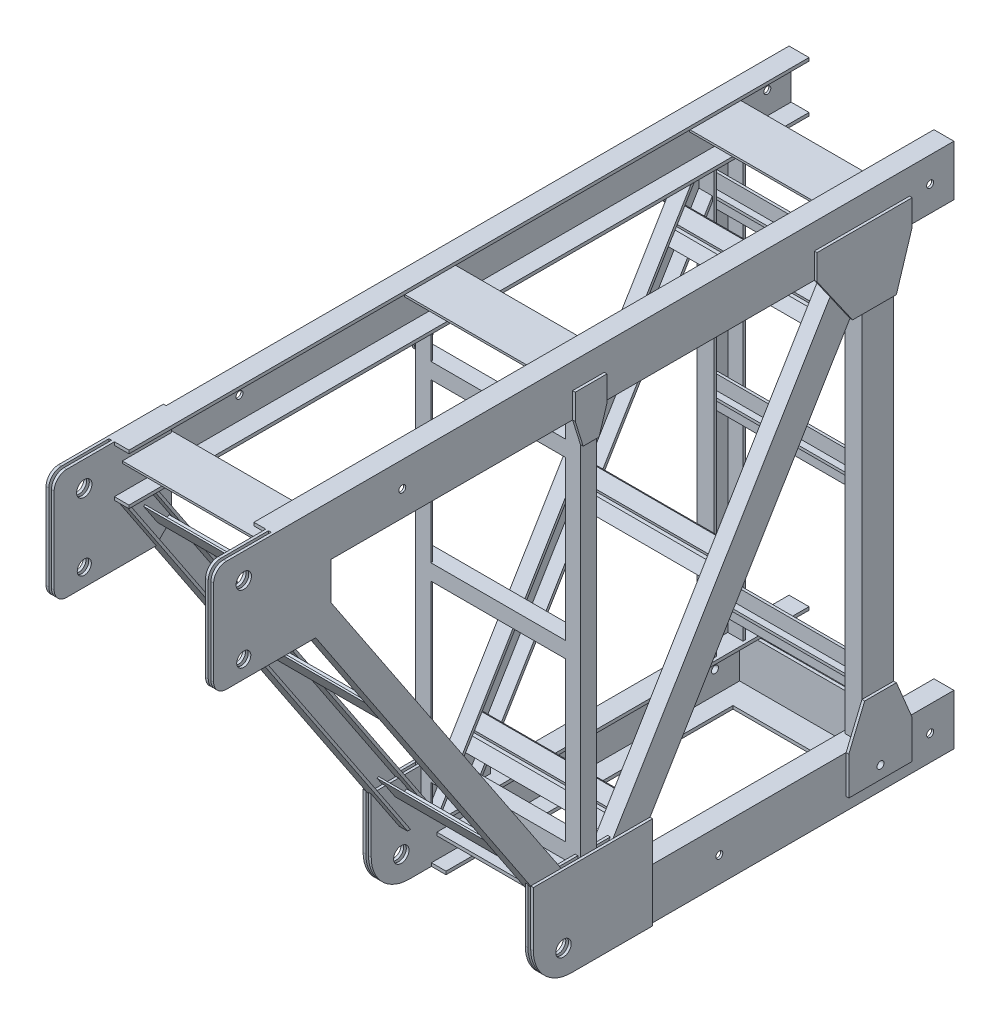
SolidWorks part; units mm, degrees
note: The reader was unsure of these and kept them because the rebuilt part matched: shared geometry of "草图38<2>".
ref_plane "前视基准面" through (0, 0, 0) normal (0, 0, 1) x (1, 0, 0)
ref_plane "上视基准面" through (0, 0, 0) normal (0, 1, 0) x (1, 0, 0)
ref_plane "右视基准面" through (0, 0, 0) normal (1, 0, 0) x (0, 0, -1)
sketch "草图2" plane through (0, 0, 0) normal (0, 0, 1) x (1, 0, 0)
  line L0 (0, 0) -> (0, 160)
  line L1 (0, 160) -> (63, 160)
  line L2 (63, 160) -> (63, 150)
  line L3 (63, 150) -> (6.5, 150)
  line L4 (6.5, 150) -> (6.5, 10)
  line L5 (6.5, 10) -> (63, 10)
  line L6 (63, 10) -> (63, 0)
  line L7 (63, 0) -> (0, 0)
  line L8 (457, 160) -> (520, 160)
  line L9 (520, 160) -> (520, 0)
  line L10 (520, 0) -> (457, 0)
  line L11 (457, 0) -> (457, 10)
  line L12 (457, 10) -> (513.5, 10)
  line L13 (513.5, 10) -> (513.5, 150)
  line L14 (513.5, 150) -> (457, 150)
  line L15 (457, 150) -> (457, 160)
  dimension "D1" = 160
  dimension "D2" = 10
  dimension "D3" = 6.5
  dimension "D4" = 63
  dimension "D5" = 520
extrude "拉伸1" add sketch "草图2" along normal blind 2335
pattern_linear "阵列(线性)2" count 2 spacing 1500 along (0, -1, 0) of "拉伸1"
sketch "草图4" plane through (0, -1340, 0) normal (0, 1, 0) x (1, 0, 0)
  line L0 (0, -2335) -> (0, 0) construction
  line L1 (520, -2335) -> (0, -2335)
  line L2 (520, -2335) -> (520, -1335)
  line L3 (520, -1335) -> (0, -1335)
  line L4 (0, -2335) -> (0, -1335)
  dimension "D1" = 1000
extrude "拉伸2" cut sketch "草图4" against normal blind 1000
sketch "草图5" plane through (0, 0, 0) normal (-1, 0, 0) x (0, 0, 1)
  line L0 (160, 95) -> (320, 95)
  line L1 (320, 95) -> (320, 88.5)
  line L2 (243.25, 88.5) -> (320, 88.5)
  line L3 (243.25, 88.5) -> (243.25, 48.5)
  line L4 (243.25, 48.5) -> (236.75, 48.5)
  line L5 (236.75, 48.5) -> (236.75, 88.5)
  line L6 (236.75, 88.5) -> (160, 88.5)
  line L7 (160, 88.5) -> (160, 95)
  line L8 (0, 160) -> (0, 0) construction
  point P10 (0, 80)
  dimension "D1" = 160
  dimension "D2" = 6.5
  dimension "D3" = 6.5
  dimension "D4" = 40
  dimension "D5" = 160
  dimension "D6" = 15
extrude "拉伸3" add sketch "草图5" against normal blind 520
sketch "草图8" plane through (0, 0, 0) normal (-1, 0, 0) x (0, 0, 1)
  line L0 (240, -1420) -> (240, 160) construction
  line L1 (2335, 160) -> (0, 160) construction
  line L2 (2335, 0) -> (0, 0) construction
  line L3 (190, 0) -> (290, 0)
  line L4 (190, 0) -> (190, -1340)
  line L5 (190, -1340) -> (290, -1340)
  line L6 (290, 0) -> (290, -1340)
  line L7 (1335, -1340) -> (0, -1340) construction
  line L8 (1335, -1500) -> (0, -1500) construction
  line L9 (0, -1340) -> (0, -1500) construction
  dimension "D1" = 50
  dimension "D2" = 50
  dimension "D3" = 80
  dimension "D4" = 240
extrude "拉伸7" add sketch "草图8" against normal blind 520 separate body
sketch "草图10" plane through (0, -1340, 0) normal (0, -1, 0) x (1, 0, 0)
  line L0 (466.7, 290) -> (466.7, 281.5)
  line L1 (520, 290) -> (0, 290) construction
  line L2 (466.7, 281.5) -> (514.7, 281.5)
  line L3 (514.7, 281.5) -> (514.7, 198.5)
  line L4 (514.7, 198.5) -> (466.7, 198.5)
  line L5 (466.7, 198.5) -> (466.7, 190)
  line L6 (520, 190) -> (0, 190) construction
  line L7 (53.3, 190) -> (53.3, 198.5)
  line L8 (53.3, 198.5) -> (5.3, 198.5)
  line L9 (5.3, 198.5) -> (5.3, 281.5)
  line L10 (53.3, 281.5) -> (53.3, 290)
  line L11 (53.3, 290) -> (466.7, 290)
  line L12 (5.3, 281.5) -> (53.3, 281.5)
  line L13 (53.3, 190) -> (466.7, 190)
  line L16 (0, 1335) -> (0, 0) construction
  line L17 (520, 1335) -> (520, 0) construction
  dimension "D1" = 5.3
  dimension "D2" = 5.3
  dimension "D3" = 8.5
  dimension "D4" = 48
extrude "拉伸9" cut sketch "草图10" against normal blind 1340
sketch "草图11" plane through (0, 0, 0) normal (-1, 0, 0) x (0, 0, 1)
  line L0 (2335, 160) -> (2335, 0) construction
  line L1 (2335, 80) -> (0, 80) construction
  line L2 (0, 160) -> (0, 0) construction
  circle A0 centre (2240, 80) radius 11
  dimension "D1" = 22
  dimension "D2" = 95
extrude "拉伸10" cut sketch "草图11" against normal through all
sketch "草图12" plane through (0, 0, 0) normal (-1, 0, 0) x (0, 0, 1)
  line L0 (1145, -1420) -> (290, 0) construction
  line L1 (290, 0) -> (348.3639, 0)
  line L2 (2335, 0) -> (0, 0) construction
  line L3 (348.3639, 0) -> (1155.1949, -1340)
  line L4 (1155.1949, -1340) -> (1038.467, -1340)
  line L5 (1038.467, -1340) -> (290, -96.9319)
  line L6 (290, -1340) -> (290, 0) construction
  line L7 (290, -96.9319) -> (290, 0)
  line L8 (0, -1420) -> (1335, -1420) construction
  line L9 (1335, -1340) -> (0, -1340) construction
  line L10 (0, -1340) -> (0, -1500) construction
  line L11 (1335, -1500) -> (1335, -1340) construction
  dimension "D1" = 50
  dimension "D2" = 50
  dimension "D3" = 190
extrude "拉伸11" add sketch "草图12" against normal blind 48
pattern_linear "阵列(线性)3" count 2 spacing 472 along (1, 0, 0) of "拉伸11"
sketch "草图13" plane through (48, 0, 0) normal (1, 0, 0) x (0, 0, -1)
  line L0 (-338.4421, 0) -> (-290, 0)
  line L1 (-348.3639, 0) -> (-290, 0) construction
  line L2 (-290, 0) -> (-290, -80.4535)
  line L3 (-290, 0) -> (-290, -96.9319) construction
  line L4 (-290, -80.4535) -> (-1048.3889, -1340)
  line L5 (-1038.467, -1340) -> (-1155.1949, -1340) construction
  line L6 (-1048.3889, -1340) -> (-1145.2731, -1340)
  line L7 (-1145.2731, -1340) -> (-338.4421, 0)
  line L8 (-1155.1949, -1340) -> (-348.3639, 0) construction
  line L9 (-290, -96.9319) -> (-1038.467, -1340) construction
  dimension "D1" = 8.5
  dimension "D2" = 8.5
extrude "拉伸12" cut sketch "草图13" against normal blind 42.7
sketch "草图14" plane through (472, 0, 0) normal (-1, 0, 0) x (0, 0, 1)
  line L0 (290, -80.4535) -> (290, 0)
  line L1 (290, 0) -> (290, -96.9319) construction
  line L2 (290, 0) -> (338.4421, 0)
  line L3 (348.3639, 0) -> (290, 0) construction
  line L4 (338.4421, 0) -> (1145.2731, -1340)
  line L5 (1038.467, -1340) -> (1155.1949, -1340) construction
  line L6 (1145.2731, -1340) -> (1048.3889, -1340)
  line L7 (1048.3889, -1340) -> (290, -80.4535)
  line L8 (1155.1949, -1340) -> (348.3639, 0) construction
  line L9 (290, -96.9319) -> (1038.467, -1340) construction
  dimension "D1" = 8.5
  dimension "D2" = 8.5
extrude "拉伸13" cut sketch "草图14" against normal blind 42.7
sketch "草图15" plane through (0, 0, 0) normal (-1, 0, 0) x (0, 0, 1)
  line L0 (2145, 80) -> (1145, -1420) construction
  line L1 (2091.6667, 0) -> (2043.5926, 0)
  line L2 (2335, 0) -> (348.3639, 0) construction
  line L3 (2043.5926, 0) -> (1152.8527, -1336.11)
  line L4 (1155.1949, -1340) -> (348.3639, 0) construction
  line L5 (1152.8527, -1336.11) -> (1155.1949, -1340)
  line L6 (1155.1949, -1340) -> (1246.4074, -1340)
  line L7 (1335, -1340) -> (1155.1949, -1340) construction
  line L8 (1246.4074, -1340) -> (2139.7407, 0)
  line L9 (2139.7407, 0) -> (2091.6667, 0)
  line L10 (0, -1420) -> (1335, -1420) construction
  line L11 (2240, 80) -> (0, 80) construction
  line L12 (0, 160) -> (0, 0) construction
  line L13 (0, -1340) -> (0, -1500) construction
  line L14 (1335, -1500) -> (1335, -1340) construction
  dimension "D1" = 40
  dimension "D2" = 40
  dimension "D3" = 190
  dimension "D4" = 95
extrude "拉伸14" add sketch "草图15" against normal blind 43
pattern_linear "阵列(线性)4" count 2 spacing 477 along (1, 0, 0) of "拉伸14"
sketch "草图16" plane through (477, 0, 0) normal (-1, 0, 0) x (0, 0, 1)
  line L0 (2053.2075, 0) -> (2130.1259, 0)
  line L1 (2139.7407, 0) -> (2043.5926, 0) construction
  line L2 (2130.1259, 0) -> (1236.7925, -1340)
  line L3 (1155.1949, -1340) -> (1246.4074, -1340) construction
  line L4 (1236.7925, -1340) -> (1159.8741, -1340)
  line L5 (1159.8741, -1340) -> (2053.2075, 0)
  line L6 (1246.4074, -1340) -> (2139.7407, 0) construction
  line L7 (2043.5926, 0) -> (1152.8527, -1336.11) construction
  dimension "D1" = 8
  dimension "D2" = 8
extrude "拉伸15" cut sketch "草图16" against normal blind 38
sketch "草图17" plane through (43, 0, 0) normal (1, 0, 0) x (0, 0, -1)
  line L0 (-2130.1259, 0) -> (-2053.2075, 0)
  line L1 (-2139.7407, 0) -> (-2043.5926, 0) construction
  line L2 (-2053.2075, 0) -> (-1159.8741, -1340)
  line L3 (-1155.1949, -1340) -> (-1246.4074, -1340) construction
  line L4 (-1159.8741, -1340) -> (-1236.7925, -1340)
  line L5 (-1236.7925, -1340) -> (-2130.1259, 0)
  line L6 (-1246.4074, -1340) -> (-2139.7407, 0) construction
  line L7 (-2043.5926, 0) -> (-1152.8527, -1336.11) construction
  dimension "D1" = 8
  dimension "D2" = 8
extrude "拉伸16" cut sketch "草图17" against normal blind 38
sketch "草图18" plane through (0, 0, 0) normal (-1, 0, 0) x (0, 0, 1)
  line L0 (1152.8527, -1336.11) -> (1152.8527, 0.0067) construction
  line L1 (1152.8527, -1336.11) -> (348.3639, 0) construction
  line L2 (2043.5926, 0) -> (348.3639, 0) construction
  line L4 (1127.8527, 0) -> (1177.8527, 0)
  line L5 (1127.8527, 0) -> (1127.8527, -1294.5895)
  line L7 (1177.8527, 0) -> (1177.8527, -1298.61)
  line L8 (2043.5926, 0) -> (1152.8527, -1336.11) construction
  line L9 (1177.8527, -1298.61) -> (1152.8527, -1336.11)
  line L10 (1152.8527, -1336.11) -> (1127.8527, -1294.5895)
  dimension "D1" = 25
  dimension "D2" = 25
extrude "拉伸17" add sketch "草图18" against normal blind 520 separate body
sketch "草图19" plane through (0, 0, 0) normal (0, 1, 0) x (1, 0, 0)
  line L0 (457, -2335) -> (457, 0) construction
  line L1 (457, -1127.8527) -> (63, -1127.8527)
  line L2 (457, -1127.8527) -> (457, -1177.8527)
  line L3 (457, -1177.8527) -> (63, -1177.8527)
  line L4 (63, -1127.8527) -> (63, -1177.8527)
  line L5 (520, -1127.8527) -> (0, -1127.8527) construction
  line L6 (520, -1177.8527) -> (0, -1177.8527) construction
  line L7 (63, -2335) -> (63, 0) construction
extrude "拉伸18" cut sketch "草图19" against normal through all
sketch "草图20" plane through (457, 0, 0) normal (-1, 0, 0) x (0, 0, 1)
  line L0 (1127.8527, 0) -> (1177.8527, 0)
  line L1 (1177.8527, 0) -> (1177.8527, -1298.61)
  line L2 (1177.8527, -1298.61) -> (1152.8527, -1336.11)
  line L3 (1152.8527, -1336.11) -> (1127.8527, -1294.5895)
  line L4 (1127.8527, -1294.5895) -> (1152.8527, -1336.11) construction
  line L5 (1127.8527, -1294.5895) -> (1127.8527, 0) construction
  line L6 (1127.8527, -1294.5895) -> (1127.8527, 0)
extrude "拉伸19" cut sketch "草图20" against normal blind 15
sketch "草图21" plane through (63, 0, 0) normal (1, 0, 0) x (0, 0, -1)
  line L0 (-1177.8527, -1298.61) -> (-1152.8527, -1336.11)
  line L1 (-1152.8527, -1336.11) -> (-1127.8527, -1294.5895)
  line L2 (-1127.8527, -1294.5895) -> (-1127.8527, 0)
  line L3 (-2335, 0) -> (0, 0) construction
  line L4 (-1127.8527, -1294.5895) -> (-1127.8527, 0) construction
  line L5 (-1127.8527, 0) -> (-1177.8527, 0)
  line L6 (-1127.8527, 0) -> (-1177.8527, 0) construction
  line L7 (-1177.8527, 0) -> (-1177.8527, -1298.61)
extrude "拉伸20" cut sketch "草图21" against normal blind 15
sketch "草图23" plane through (472, 0, 0) normal (-1, 0, 0) x (0, 0, 1)
  line L0 (1172.8527, -1306.11) -> (1152.8527, -1336.11)
  line L1 (1152.8527, -1336.11) -> (1177.8527, -1298.61) construction
  line L2 (1152.8527, -1336.11) -> (1127.8527, -1294.5895)
  line L3 (1127.8527, -1294.5895) -> (1127.8527, 0)
  line L4 (1177.8527, 0) -> (1127.8527, 0) construction
  line L5 (1127.8527, 0) -> (1172.8527, 0)
  line L6 (1172.8527, 0) -> (1172.8527, -1306.11)
  line L8 (1177.8527, -1298.61) -> (1177.8527, 0) construction
  dimension "D1" = 5
extrude "拉伸21" cut sketch "草图23" against normal blind 45
sketch "草图24" plane through (48, 0, 0) normal (1, 0, 0) x (0, 0, -1)
  line L0 (-1172.8527, -1306.11) -> (-1152.8527, -1336.11)
  line L1 (-1177.8527, -1298.61) -> (-1152.8527, -1336.11) construction
  line L2 (-1152.8527, -1336.11) -> (-1127.8527, -1294.5895)
  line L3 (-1127.8527, -1294.5895) -> (-1127.8527, 0)
  line L4 (-1127.8527, 0) -> (-1172.8527, 0)
  line L5 (-1127.8527, 0) -> (-1177.8527, 0) construction
  line L6 (-1172.8527, 0) -> (-1172.8527, -1306.11)
  line L7 (-1177.8527, 0) -> (-1177.8527, -1298.61) construction
  dimension "D1" = 5
extrude "拉伸22" cut sketch "草图24" against normal blind 45
pattern_linear "阵列(线性)6" count 3 spacing 900 along (0, 0, 1) of "拉伸3"
sketch "草图27" plane through (0, -1500, 0) normal (0, -1, 0) x (1, 0, 0)
  line L0 (0, 1335) -> (0, 0) construction
  line L1 (0, 240) -> (520, 240)
  line L2 (0, 240) -> (0, 80)
  line L3 (0, 80) -> (520, 80)
  line L4 (520, 240) -> (520, 80)
  line L5 (520, 1335) -> (520, 0) construction
  line L6 (0, 0) -> (63, 0) construction
  line L12 (0, 160) -> (520, 160) construction
  dimension "D1" = 160
  dimension "D2" = 80
extrude "拉伸24" add sketch "草图27" against normal blind 10
sketch "草图28" plane through (0, -1490, 0) normal (0, 1, 0) x (1, 0, 0)
  line L0 (513.5, -1335) -> (513.5, 0) construction
  line L1 (513.5, -162.5) -> (6.5, -162.5)
  line L2 (513.5, -162.5) -> (513.5, -152.5)
  line L3 (513.5, -152.5) -> (6.5, -152.5)
  line L4 (6.5, -162.5) -> (6.5, -152.5)
  line L5 (6.5, -1335) -> (6.5, 0) construction
  line L6 (63, -240) -> (63, -80) construction
  line L7 (457, -240) -> (457, -80) construction
  line L8 (63, -80) -> (457, -80) construction
  line L9 (457, -160) -> (63, -160) construction
  dimension "D1" = 10
  dimension "D2" = 5
extrude "拉伸25" add sketch "草图28" along normal blind 140
sketch "草图29" plane through (0, 0, 0) normal (-1, 0, 0) x (0, 0, 1)
  line L0 (240, -1340) -> (190, -1340) construction
  line L1 (240, -1340) -> (240, 160) construction
  line L2 (2335, 160) -> (0, 160) construction
  line L3 (231.5, -1160) -> (231.5, -1260)
  line L4 (231.5, -1260) -> (240, -1260)
  line L5 (240, -1260) -> (240, -1214.25)
  line L6 (240, -1214.25) -> (260, -1214.25)
  line L7 (260, -1214.25) -> (260, -1205.75)
  line L8 (260, -1205.75) -> (240, -1205.75)
  line L9 (240, -1205.75) -> (240, -1160)
  line L10 (240, -1160) -> (231.5, -1160)
  line L11 (190, 0) -> (190, -1340) construction
  line L12 (240, -1340) -> (290, -1340) construction
  dimension "D1" = 100
  dimension "D2" = 8.5
  dimension "D3" = 8.5
  dimension "D4" = 20
  dimension "D5" = 80
extrude "拉伸26" add sketch "草图29" against normal blind 520
pattern_linear "阵列(线性)9" count 3 spacing 550 along (0, 1, 0) of "拉伸26"
sketch "草图30" plane through (0, 0, 0) normal (-1, 0, 0) x (0, 0, 1)
  line L0 (1193.169, -1500) -> (193.662, 160) construction
  line L1 (1335, -1500) -> (0, -1500) construction
  line L2 (2335, 160) -> (0, 160) construction
  line L3 (290, -96.9319) -> (1038.467, -1340) construction
  line L5 (290, -96.9319) -> (332.8347, -71.1406) construction
  line L6 (332.8347, -71.1406) -> (375.6693, -45.3493) construction
  line L7 (1152.8527, -1336.11) -> (348.3639, 0) construction
  line L8 (339.5134, -98.7113) -> (391.096, -184.3806)
  line L9 (391.096, -184.3806) -> (398.3779, -179.9961)
  line L10 (398.3779, -179.9961) -> (374.7789, -140.8024)
  line L11 (374.7789, -140.8024) -> (391.9128, -130.4859)
  line L12 (391.9128, -130.4859) -> (387.5282, -123.204)
  line L13 (387.5282, -123.204) -> (370.3944, -133.5205)
  line L14 (370.3944, -133.5205) -> (346.7953, -94.3268)
  line L15 (346.7953, -94.3268) -> (339.5134, -98.7113)
  dimension "D1" = 100
  dimension "D2" = 8.5
  dimension "D3" = 8.5
  dimension "D4" = 20
  dimension "D5" = 80
extrude "拉伸27" add sketch "草图30" against normal blind 520
pattern_linear "阵列(线性)10" count 3 spacing 620 along (0, -0.8567, 0.5158) of "拉伸27"
sketch "草图31" plane through (520, 0, 0) normal (1, 0, 0) x (0, 0, -1)
  line L0 (-2048.9085, -59.6303) -> (-2004.5325, -126.1943)
  line L1 (-2048.9085, -59.6303) -> (-2053.0688, -62.4038)
  line L2 (-2004.5325, -126.1943) -> (-2008.6928, -128.9678)
  line L3 (-2053.0688, -62.4038) -> (-2008.6928, -128.9678)
  line L4 (-1246.4074, -1340) -> (-1213.1253, -1317.812) construction
  line L5 (-1213.1253, -1317.812) -> (-1179.8433, -1295.624) construction
  line L6 (-2198.3333, 160) -> (-1213.1253, -1317.812) construction
  line L7 (-2335, 160) -> (0, 160) construction
  line L8 (-1246.4074, -1340) -> (-2139.7407, 0) construction
  line L10 (-2043.5926, 0) -> (-1152.8527, -1336.11) construction
  line L11 (-2053.0688, -62.4038) -> (-2028.8006, -94.299) construction
  line L12 (-2048.9085, -59.6303) -> (-2008.6928, -128.9678) construction
  line L13 (-2028.8006, -94.299) -> (-2004.5325, -126.1943) construction
  dimension "D1" = 80
  dimension "D2" = 5
  dimension "D3" = 100
extrude "拉伸28" add sketch "草图31" against normal blind 520
sketch "草图32" plane through (0, -963.9979, 1445.9968) normal (0, 0.5547, -0.8321) x (-1, 0, 0)
  line L0 (-5, 1086.9146) -> (-515, 1086.9146) construction
  line L1 (-460, 1049.4146) -> (-60, 1049.4146)
  line L2 (-460, 1049.4146) -> (-460, 1044.4146)
  line L3 (-460, 1044.4146) -> (-60, 1044.4146)
  line L4 (-60, 1049.4146) -> (-60, 1044.4146)
  line L9 (-5, 1046.9146) -> (-515, 1046.9146) construction
  line L11 (-515, 1006.9146) -> (-515, 1086.9146) construction
  line L12 (-260, 1046.9146) -> (-260, 1086.9146) construction
  line L13 (-5, 1086.9146) -> (-515, 1086.9146) construction
  dimension "D1" = 2.5
  dimension "D2" = 2.5
  dimension "D3" = 200
  dimension "D4" = 200
extrude "拉伸29" add sketch "草图32" along normal blind 15
pattern_linear "阵列(线性)11" count 3 spacing 675 along (0, -0.8321, -0.5547) of "拉伸28", "拉伸29"
sketch "草图38" plane through (0, 0, 1177.8527) normal (0, 0, 1) x (1, 0, 0)
  line L0 (0, -1298.61) -> (0, 0) construction
  line L1 (0, -1188.61) -> (520, -1188.61)
  line L2 (0, -1188.61) -> (0, -1238.61)
  line L3 (0, -1238.61) -> (520, -1238.61)
  line L4 (520, -1188.61) -> (520, -1238.61)
  line L5 (520, -1298.61) -> (520, 0) construction
  dimension "D1" = 50
  dimension "D2" = 60
extrude "拉伸36" add sketch "草图38" against normal blind 50
extrude "拉伸37" add sketch "草图38<2>" against normal blind 50
sketch "草图38<2>" plane through (0, 0, 1177.8527) normal (0, 0, 1) x (1, 0, 0) same geometry as "草图38"
pattern_linear "阵列(线性)13" count 3 spacing 550 along (0, 1, 0) of "拉伸37"
sketch "草图39" plane through (0, 0, 1127.8527) normal (0, 0, -1) x (-1, 0, 0)
  line L0 (-3, -1294.5895) -> (-3, -1238.61) construction
  line L1 (-517, -1238.61) -> (-3, -1238.61)
  line L2 (-517, -1238.61) -> (-517, -1193.61)
  line L3 (-517, -1193.61) -> (-3, -1193.61)
  line L4 (-3, -1238.61) -> (-3, -1193.61)
  line L6 (-517, -688.61) -> (-3, -688.61)
  line L7 (-517, -688.61) -> (-517, -643.61)
  line L8 (-517, -643.61) -> (-3, -643.61)
  line L9 (-3, -688.61) -> (-3, -643.61)
  line L10 (-517, -138.61) -> (-3, -138.61)
  line L11 (-517, -138.61) -> (-517, -93.61)
  line L12 (-517, -93.61) -> (-3, -93.61)
  line L13 (-3, -138.61) -> (-3, -93.61)
  dimension "D1" = 45
extrude "拉伸38" cut sketch "草图39" against normal blind 45
sketch "草图40" plane through (520, 0, 0) normal (1, 0, 0) x (0, 0, -1)
  line L0 (-1246.4074, -1340) -> (-2139.7407, 0) construction
  line L1 (-1335, -1500) -> (-958.4529, -1500)
  line L2 (-1335, -1500) -> (-1335, -1207.111)
  line L3 (-1335, -1207.111) -> (-958.4529, -1207.111)
  line L4 (-958.4529, -1500) -> (-958.4529, -1207.111)
  line L5 (-290, -96.9319) -> (-1038.467, -1340) construction
extrude "拉伸39" add sketch "草图40" along normal blind 8.5
pattern_linear "阵列(线性)15" count 2 spacing 17 along (-1, 0, 0) of "拉伸39"
pattern_linear "阵列(线性)16" count 2 spacing 511.5 along (-1, 0, 0) of "拉伸39", "阵列(线性)15"
sketch "草图41" plane through (0, 0, 1335) normal (0, 0, 1) x (1, 0, 0)
  line L0 (63, -1500) -> (-8.5, -1500) construction
  line L1 (8.5, -1500) -> (0, -1500)
  line L2 (8.5, -1500) -> (8.5, -1340)
  line L3 (8.5, -1340) -> (0, -1340)
  line L4 (0, -1500) -> (0, -1340)
  line L5 (8.5, -1340) -> (0, -1340) construction
  line L6 (8.5, -1350) -> (8.5, -1490) construction
  line L7 (528.5, -1500) -> (457, -1500) construction
  line L8 (17, -1340) -> (503, -1340)
  line L9 (17, -1340) -> (17, -1500)
  line L10 (17, -1500) -> (503, -1500)
  line L11 (503, -1340) -> (503, -1500)
  line L12 (503, -1350) -> (503, -1490) construction
  line L13 (520, -1340) -> (511.5, -1340) construction
  line L14 (511.5, -1340) -> (520, -1340)
  line L15 (511.5, -1340) -> (511.5, -1500)
  line L16 (511.5, -1500) -> (520, -1500)
  line L17 (520, -1340) -> (520, -1500)
  line L18 (511.5, -1350) -> (511.5, -1490) construction
  line L19 (63, -1340) -> (17, -1340) construction
  line L20 (17, -1350) -> (17, -1490) construction
  dimension "D1" = 8.5
extrude "拉伸40" cut sketch "草图41" against normal blind 190
sketch "草图42" plane through (503, 0, 0) normal (-1, 0, 0) x (0, 0, 1)
  line L0 (958.4529, -1420) -> (1335, -1420) construction
  line L1 (967.8527, -1415) -> (1127.8527, -1415)
  line L2 (967.8527, -1415) -> (967.8527, -1425)
  line L3 (967.8527, -1425) -> (1127.8527, -1425)
  line L4 (1127.8527, -1415) -> (1127.8527, -1425)
  line L5 (958.4529, -1490) -> (958.4529, -1350) construction
  line L8 (1127.8527, 0) -> (1127.8527, -1207.111) construction
  dimension "D1" = 10
  dimension "D2" = 160
  dimension "D3" = 5
extrude "拉伸41" add sketch "草图42" along normal blind 501.5
fillet "圆角1" radius 120 4 edges at (524.25, -1500, 1335) (-4.25, -1500, 1335) (12.75, -1500, 1335) (507.25, -1500, 1335)
sketch "草图43" plane through (-8.5, 0, 0) normal (-1, 0, 0) x (0, 0, 1)
  line L0 (1215, -1500) -> (958.4529, -1500) construction
  line L1 (1335, -1207.111) -> (1335, -1380) construction
  circle A0 centre (1240, -1420) radius 24.25
  dimension "D1" = 48.5
  dimension "D2" = 80
  dimension "D3" = 95
extrude "拉伸42" cut sketch "草图43" against normal through all
sketch "草图44" plane through (0, 0, 0) normal (-1, 0, 0) x (0, 0, 1)
  line L1 (2335, 160) -> (1965, 160)
  line L2 (2335, 160) -> (2335, -190)
  line L3 (2335, -190) -> (1965, -190)
  line L4 (1965, 160) -> (1965, -190)
  line L5 (2043.5926, 0) -> (2110.1567, -44.376) construction
  line L6 (1335, -1207.111) -> (2139.7407, 0) construction
  line L7 (1965, -190) -> (2076.8747, -22.188) construction
  dimension "D1" = 350
extrude "拉伸43" add sketch "草图44" along normal blind 8.5
pattern_linear "阵列(线性)17" count 2 spacing 17 along (1, 0, 0) of "拉伸43"
sketch "草图45" plane through (0, 0, 2335) normal (0, 0, 1) x (1, 0, 0)
  line L0 (63, 160) -> (-8.5, 160) construction
  line L1 (0, -190) -> (8.5, -190)
  line L2 (0, -190) -> (0, 160)
  line L3 (0, 160) -> (8.5, 160)
  line L4 (8.5, -190) -> (8.5, 160)
  line L5 (8.5, -190) -> (8.5, 0) construction
  line L6 (520, 160) -> (457, 160) construction
  line L7 (17, -190) -> (513.5, -190)
  line L8 (17, -190) -> (17, 160)
  line L9 (17, 160) -> (513.5, 160)
  line L10 (513.5, -190) -> (513.5, 160)
  line L11 (513.5, 150) -> (513.5, 10) construction
extrude "拉伸44" cut sketch "草图45" against normal blind 190
chamfer "倒角1" distance 50 angle 45 2 edges at (-4.25, -190, 1965) (12.75, -190, 1965)
sketch "草图46" plane through (-8.5, 0, 0) normal (-1, 0, 0) x (0, 0, 1)
  line L0 (2335, 160) -> (1965, 160) construction
  line L2 (2335, -190) -> (2335, 160) construction
  line L3 (2240, 80) -> (2240, -190) construction
  line L4 (2015, -190) -> (2335, -190) construction
  circle A0 centre (2240, 80) radius 24.25
  dimension "D1" = 48.5
  dimension "D2" = 80
  dimension "D3" = 95
extrude "拉伸45" cut sketch "草图46" against normal through all
sketch "草图47" plane through (0, 0, 0) normal (-1, 0, 0) x (0, 0, 1)
  line L0 (140, 80) -> (140, 0)
  line L1 (190, 0) -> (0, 0) construction
  line L2 (140, 0) -> (190, -160)
  line L3 (190, -160) -> (327.9741, -160)
  line L5 (327.9741, -160) -> (440, 0)
  line L6 (1127.8527, 0) -> (348.3639, 0) construction
  line L7 (440, 0) -> (440, 80)
  line L8 (440, 80) -> (140, 80)
  line L9 (190, 0) -> (190, -1340) construction
  line L10 (190, 0) -> (190, -1340) construction
  line L11 (0, 80) -> (1965, 80) construction
  line L12 (0, 160) -> (0, 0) construction
  line L13 (1965, 160) -> (1965, 0) construction
  line L14 (190, 0) -> (190, -160) construction
  line L15 (290, -96.9319) -> (958.4529, -1207.111) construction
  line L17 (958.4529, -1500) -> (0, -1500) construction
  line L21 (140, -1460) -> (340, -1460)
  line L22 (340, -1460) -> (340, -1340)
  line L24 (958.4529, -1340) -> (290, -1340) construction
  line L26 (340, -1340) -> (290, -1220)
  line L27 (290, -1340) -> (290, -96.9319) construction
  line L29 (290, -1220) -> (190, -1220)
  line L30 (190, -1220) -> (140, -1340)
  line L31 (190, -1340) -> (0, -1340) construction
  line L32 (140, -1340) -> (140, -1460)
  line L33 (1127.8527, 0) -> (1177.8527, 0) construction
  line L34 (1177.8527, 0) -> (1177.8527, -1207.111) construction
  line L35 (1152.8527, 0) -> (1152.8527, -1207.111) construction
  line L36 (1127.8527, -1207.111) -> (1177.8527, -1207.111) construction
  line L37 (1102.8527, 80) -> (1202.8527, 80)
  line L38 (1202.8527, 80) -> (1202.8527, 0)
  line L39 (1965, 0) -> (1177.8527, 0) construction
  line L40 (1202.8527, 0) -> (1177.8527, -80)
  line L41 (1177.8527, -80) -> (1127.8527, -80)
  line L42 (1127.8527, 0) -> (1127.8527, -1207.111) construction
  line L43 (1127.8527, -80) -> (1102.8527, 0)
  line L44 (1102.8527, 0) -> (1102.8527, 80)
  line L45 (1102.8527, 80) -> (1152.8527, 0) construction
  line L46 (1202.8527, 80) -> (1152.8527, 0) construction
  dimension "D1" = 300
  dimension "D2" = 50
  dimension "D3" = 120
  dimension "D4" = 200
  dimension "D5" = 40
  dimension "D6" = 100
  dimension "D7" = 80
extrude "拉伸46" add sketch "草图47" along normal blind 8.5
pattern_linear "阵列(线性)19" count 2 spacing 528.5 along (1, 0, 0) of "拉伸46"
sketch "草图49" plane through (0, 160, 0) normal (0, 1, 0) x (1, 0, 0)
  line L0 (513.5, -2145) -> (457, -2145) construction
  line L1 (494.5, -1965) -> (503, -1965)
  line L2 (494.5, -1965) -> (494.5, -2335)
  line L3 (494.5, -2335) -> (503, -2335)
  line L4 (503, -1965) -> (503, -2335)
  line L6 (520, -2335) -> (520, 0) construction
  dimension "D1" = 370
  dimension "D2" = 180
  dimension "D3" = 8.5
  dimension "D4" = 17
extrude "拉伸48" add sketch "草图49" against normal blind 350
sketch "草图50" plane through (494.5, 0, 0) normal (-1, 0, 0) x (0, 0, 1)
  line L0 (1965, -132.3112) -> (1965, -190)
  line L1 (1965, -190) -> (2003.4592, -190)
  line L2 (2003.4592, -190) -> (1965, -132.3112)
extrude "拉伸50" cut sketch "草图50" against normal blind 8.5
pattern_linear "阵列(线性)21" count 2 spacing 17 along (1, 0, 0) of "拉伸48"
sketch "草图52" plane through (520, 0, 0) normal (1, 0, 0) x (0, 0, -1)
  line L0 (-2335, 160) -> (0, 160) construction
  line L1 (-2335, -190) -> (-2335, 160) construction
  line L2 (-2240, 80) -> (-2240, -190) construction
  line L3 (-2335, -190) -> (-2013.074, -190) construction
  circle A0 centre (-2240, 80) radius 24.25
  circle A1 centre (-2240, -135) radius 22.25
  dimension "D1" = 48.5
  dimension "D4" = 44.5
  dimension "D2" = 80
  dimension "D3" = 95
  dimension "D5" = 215
extrude "拉伸54" cut sketch "草图52" against normal through all
fillet "圆角2" radius 40 8 edges at (-4.25, -190, 2335) (12.75, -190, 2335) (-4.25, 160, 2335) (12.75, 160, 2335) (515.75, 160, 2335) (498.75, 160, 2335) (498.75, -190, 2335) (515.75, -190, 2335)
sketch "草图53" plane through (-8.5, 0, 0) normal (-1, 0, 0) x (0, 0, 1)
  line L0 (1240, -1420) -> (0, -1420) construction
  line L1 (0, -1340) -> (0, -1500) construction
  line L2 (2240, 80) -> (0, 80) construction
  line L3 (0, 160) -> (0, 0) construction
  circle A0 centre (1740, 80) radius 11
  circle A1 centre (740, -1420) radius 11
  circle A2 centre (240, -1420) radius 11
  circle A3 centre (75, -1420) radius 11
  circle A4 centre (75, 80) radius 11
  dimension "D1" = 22
  dimension "D2" = 500
  dimension "D3" = 500
  dimension "D4" = 500
  dimension "D5" = 75
  dimension "D6" = 75
extrude "拉伸55" cut sketch "草图53" against normal through all
